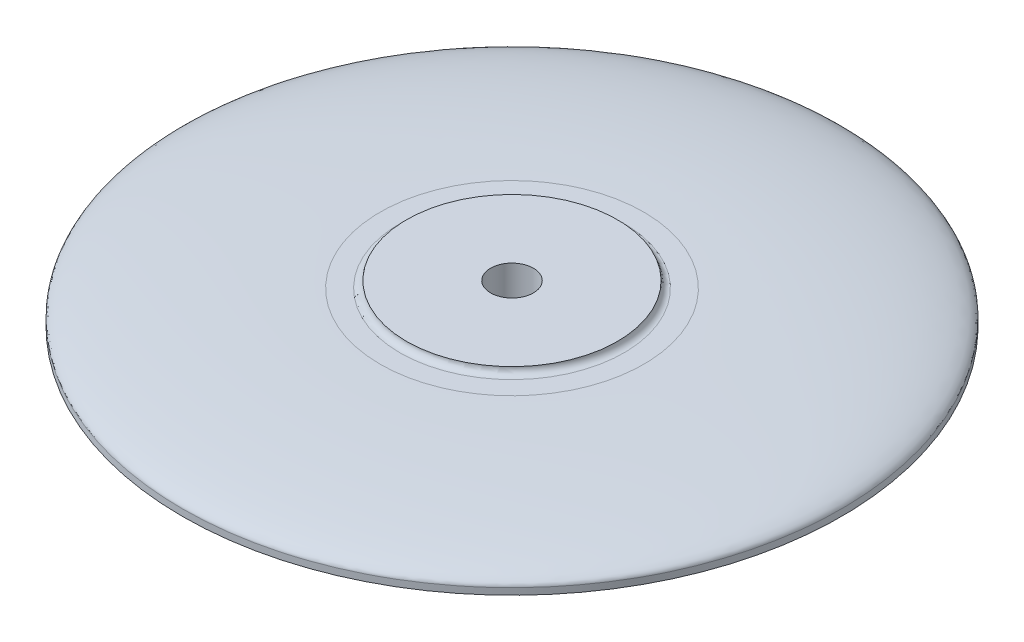
SolidWorks part; units mm, degrees
ref_plane "Front Plane" through (0, 0, 0) normal (0, 0, 1) x (1, 0, 0)
ref_plane "Top Plane" through (0, 0, 0) normal (0, 1, 0) x (1, 0, 0)
ref_plane "Right Plane" through (0, 0, 0) normal (1, 0, 0) x (0, 0, -1)
sketch "Sketch1" plane through (0, 0, 0) normal (0, 1, 0) x (1, 0, 0)
  circle A0 centre (0, 0) radius 50
  dimension "D1" = 100
extrude "Boss-Extrude1" add sketch "Sketch1" along normal blind 5
sketch "Sketch2" plane through (0, 5, 0) normal (0, 1, 0) x (1, 0, 0)
  circle A0 centre (0, 0) radius 16
  dimension "D1" = 32
extrude "Boss-Extrude2" add sketch "Sketch2" along normal blind 1
sketch "Sketch3" plane through (0, 6, 0) normal (0, 1, 0) x (1, 0, 0)
  circle A0 centre (0, 0) radius 3.25
  dimension "D1" = 6.5
extrude "Cut-Extrude1" cut sketch "Sketch3" against normal through all
fillet "Fillet1" radius 1 1 edges at (0, 5, 16)
fillet "Fillet2" radius 4 1 edges at (0, 5, 50) second distance 30 first distance on face at (0, 5, 50)
